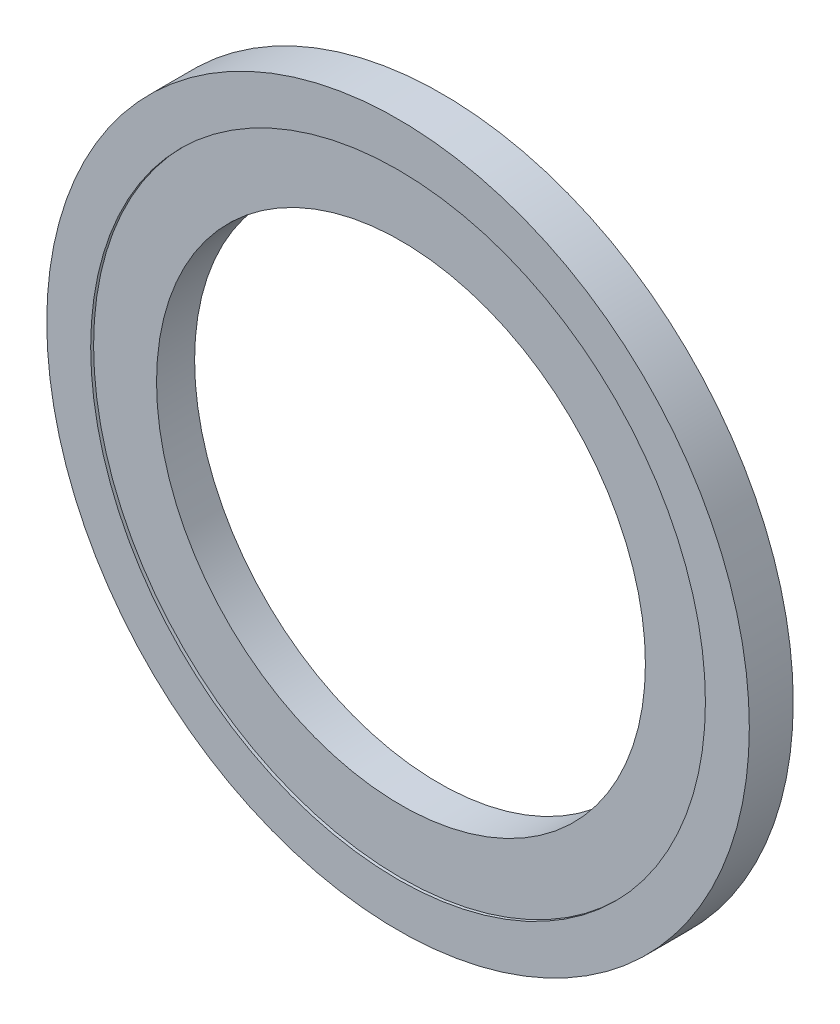
SolidWorks part; units mm, degrees
material "Zinc AC43A (Zn-4Al-2.5Cu-0.04Mg; Number 2 Die Casting Alloy; Zamak 2), Die Cast"
ref_plane "Front" through (0, 0, 0) normal (0, 0, 1) x (1, 0, 0)
ref_plane "Top" through (0, 0, 0) normal (0, 1, 0) x (1, 0, 0)
ref_plane "Right" through (0, 0, 0) normal (1, 0, 0) x (0, 0, -1)
ref_axis "Axis1" through (-84.4107, 0, 0) along (1, 0, 0)
ref_axis "Axis2" through (0, 64.3378, 0) along (0, -1, 0)
ref_axis "Axis3" through (0, 0, -102.329) along (0, 0, 1)
sketch "Sketch1" plane through (0, 0, 0) normal (0, 0, 1) x (1, 0, 0)
  circle A0 centre (0, 0) radius 12
  circle A1 centre (0, 0) radius 8.35
  dimension "D1" = 24
  dimension "D2" = 16.7
extrude "Boss-Extrude1" add sketch "Sketch1" along normal blind 1.5
sketch "Sketch3" plane through (0, 0, 1.5) normal (0, 0, 1) x (1, 0, 0)
  circle A0 centre (0, 0) radius 10.5
  dimension "D1" = 21
extrude "Cut-Extrude1" cut sketch "Sketch3" against normal blind 0.1
sketch "Sketch4" plane through (0, 0, 0) normal (0, 0, -1) x (-1, 0, 0)
  circle A0 centre (0, 0) radius 10.5
  dimension "D1" = 21
extrude "Cut-Extrude2" cut sketch "Sketch4" against normal blind 0.1
